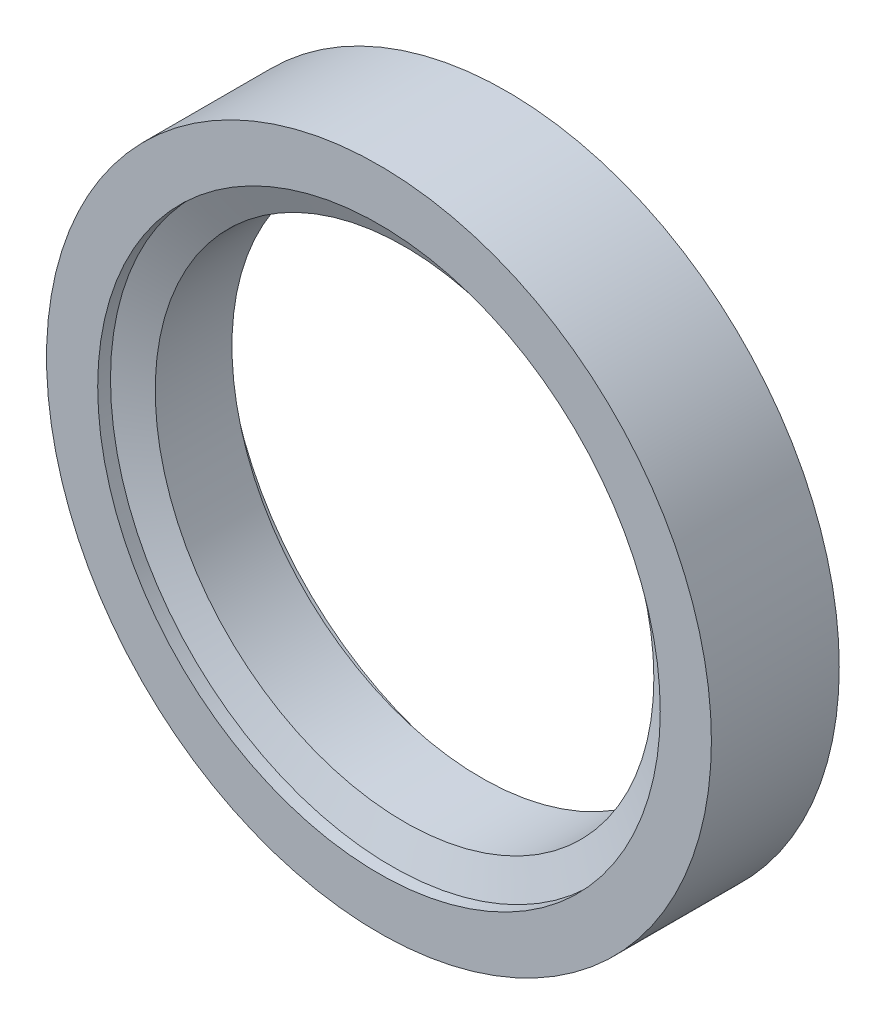
SolidWorks part; units mm, degrees
ref_plane "Спереди" through (0, 0, 0) normal (0, 0, 1) x (1, 0, 0)
ref_plane "Сверху" through (0, 0, 0) normal (0, 1, 0) x (1, 0, 0)
ref_plane "Справа" through (0, 0, 0) normal (1, 0, 0) x (0, 0, -1)
sketch "Эскиз1" plane through (0, 0, 0) normal (0, 0, 1) x (1, 0, 0)
  circle A0 centre (0, 0) radius 22
  circle A2 centre (0, 0) radius 26
  dimension "D2" = 44
  dimension "D1" = 52
extrude "Бобышка-Вытянуть1" add sketch "Эскиз1" against normal blind 5 and the other way blind 5
ref_axis "Ось1" through (0, 0, 5) along (0, 0, -1)
sketch "Эскиз2" plane through (0, 0, 0) normal (1, 0, 0) x (0, 0, -1)
  line L1 (3, 25.5) -> (4, 27.5) construction
  line L2 (-3, 25.5) -> (3, 25.5) construction
  line L3 (-4, 27.5) -> (-3, 25.5) construction
  line L4 (-4, 27.5) -> (4, 27.5)
  line L5 (3, 25.5) -> (4, 27.5)
  line L6 (-3, 25.5) -> (3, 25.5)
  line L7 (-4, 27.5) -> (-3, 25.5)
revolve "Повернуть1" [suppressed] add sketch "Эскиз2" angle 360 about axis through (0, 0, 5) along (0, 0, -1)
sketch "Эскиз5" plane through (0, 0, 0) normal (1, 0, 0) x (0, 0, -1)
  line L5 (5, 22) -> (-5, 22) construction
  line L6 (5, 22) -> (-5, 22) construction
  line L7 (-3, 19.5) -> (3, 19.5)
  line L8 (-3, 19.5) -> (-4, 22)
  line L9 (3, 19.5) -> (4, 22)
  line L10 (-4, 22) -> (4, 22)
  point P5 (0, 19.5)
  dimension "D1" = 1
  dimension "D2" = 2.5
  dimension "D3" = 1
  dimension "D4" = 1
revolve "Повернуть2" add sketch "Эскиз5" angle 360 about axis through (0, 0, 5) along (0, 0, -1)
equation "\"k\"= 1.41"
equation "\"D2@Эскиз5\"=2/0.8"
